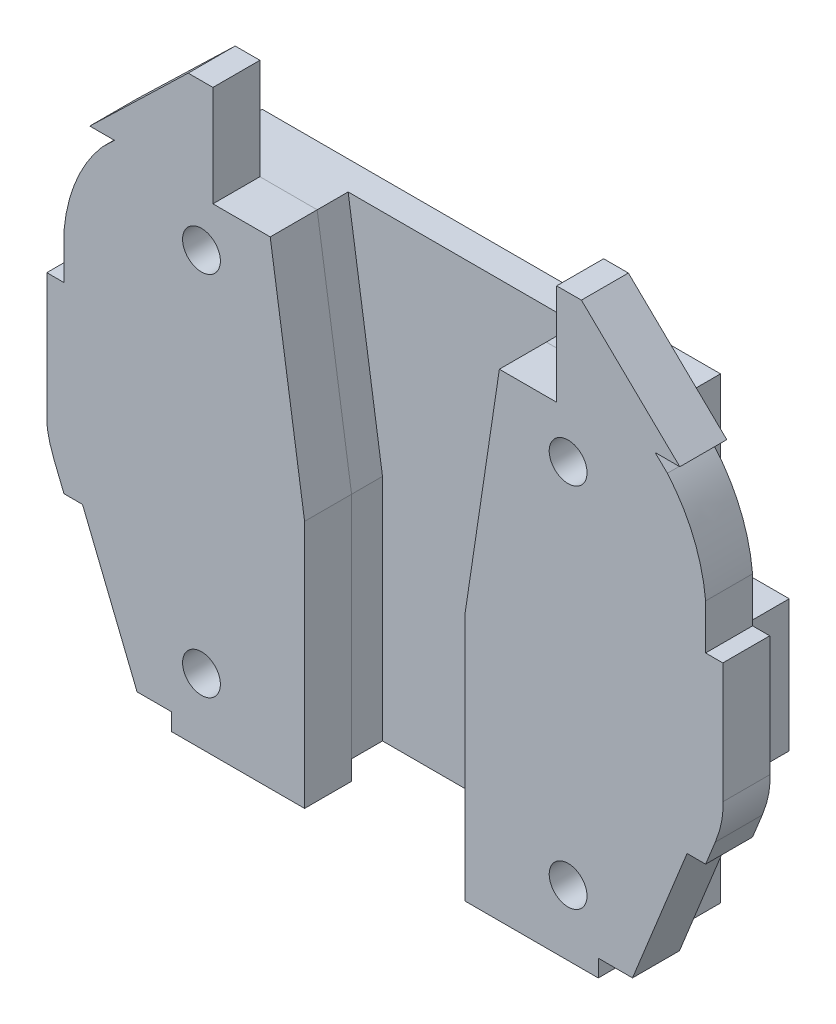
SolidWorks part; units mm, degrees
ref_plane "Front Plane" through (0, 0, 0) normal (0, 0, 1) x (1, 0, 0)
ref_plane "Top Plane" through (0, 0, 0) normal (0, 1, 0) x (1, 0, 0)
ref_plane "Right Plane" through (0, 0, 0) normal (1, 0, 0) x (0, 0, -1)
sketch "Sketch1" plane through (0, 0, 0) normal (0, 0, 1) x (1, 0, 0)
  line L0 (41, 42.4837) -> (1, 2.4837) construction
  line L1 (41, 2.4837) -> (1, 2.4837)
  line L2 (41, 2.4837) -> (41, 42.4837)
  line L3 (41, 42.4837) -> (1, 42.4837)
  line L4 (1, 2.4837) -> (1, 42.4837)
  line L5 (21, 42.4837) -> (21, 2.4837) construction
  line L6 (41, 22.4837) -> (1, 22.4837) construction
  line L7 (1, 42.4837) -> (41, 2.4837) construction
  line L9 (5, 38.4837) -> (37, 38.4837)
  line L10 (5, 38.4837) -> (5, 6.4837)
  line L11 (5, 6.4837) -> (37, 6.4837)
  line L12 (37, 38.4837) -> (37, 6.4837)
  line L13 (5, 38.4837) -> (37, 6.4837) construction
  line L14 (5, 6.4837) -> (37, 38.4837) construction
  line L40 (5, 3.0187) -> (5, 9.9487) construction
  line L41 (8, 9.4837) -> (2, 9.4837) construction
  line L42 (8, 9.4837) -> (8, 3.4837) construction
  line L43 (8, 3.4837) -> (2, 3.4837) construction
  line L44 (2, 9.4837) -> (2, 3.4837) construction
  line L45 (8, 9.4837) -> (2, 3.4837) construction
  line L46 (8, 3.4837) -> (2, 9.4837) construction
  line L47 (2, 4.7235) -> (5, 3.0187)
  line L48 (5, 3.0187) -> (8, 4.7499)
  line L49 (2, 8.2176) -> (5, 9.9487)
  line L50 (5, 9.9487) -> (8, 8.2176)
  line L51 (2, 4.7235) -> (2, 8.2176)
  line L52 (8, 4.7499) -> (8, 8.2176)
  circle A4 centre (5, 6.4837) radius 1.65
  circle A5 centre (5, 6.4837) radius 3.465 construction
  point P5 (21, 22.4837)
  point P41 (21, 22.4837)
  dimension "D2" = 40
  dimension "D3" = 40
  dimension "D1" = 32
extrude "Boss-Extrude1" add sketch "Sketch1" along normal blind 5.2 contours L4 L3 L2 L1
sketch "Sketch2" plane through (0, 0, -6) normal (0, 0, 1) x (1, 0, 0)
  line L0 (41, 2.4837) -> (41, 42.4837) construction
  line L1 (41, 10.9837) -> (1, 10.9837)
  line L2 (41, 10.9837) -> (41, 22.4837)
  line L3 (41, 22.4837) -> (1, 22.4837)
  line L4 (1, 10.9837) -> (1, 22.4837)
  line L5 (21, 22.4837) -> (21, 10.9837) construction
  line L6 (41, 16.7337) -> (1, 16.7337) construction
  line L7 (1, 2.4837) -> (1, 42.4837) construction
  line L8 (41, 42.4837) -> (1, 42.4837) construction
  line L9 (42, 22.7337) -> (0, 22.7337) construction
  point P72 (21, 16.7337)
  dimension "D1" = 11.5
  dimension "D2" = 0.25
  dimension "D3" = 20
extrude "Boss-Extrude2" add sketch "Sketch2" along normal up to surface (6 mm away) up to face at (21, 22.4837, 0)
sketch "Sketch3" plane through (0, 5.0004, 0) normal (0, -1, 0) x (1, 0, 0)
  circle A0 centre (11, -2.9068) radius 1.6
  circle A1 centre (31, -2.9068) radius 1.6
  dimension "D1" = 3.2
  dimension "D2" = 3.2
extrude "Cut-Extrude1" cut sketch "Sketch3" against normal up to surface (37.4833 mm away) up to face at (21, 42.4837, 2.6)
sketch "Sketch4" plane through (0, 0, 0) normal (0, 0, -1) x (-1, 0, 0)
  line L0 (-5, 6.4837) -> (1.6368, 6.4837) construction
  line L1 (-2.1, 9.3837) -> (-7.9, 9.3837)
  line L2 (-2.1, 9.3837) -> (-2.1, 3.5837)
  line L3 (-2.1, 3.5837) -> (-7.9, 3.5837)
  line L4 (-7.9, 9.3837) -> (-7.9, 3.5837)
  line L5 (-2.1, 9.3837) -> (-7.9, 3.5837) construction
  line L6 (-2.1, 3.5837) -> (-7.9, 9.3837) construction
  circle A0 centre (-5, 6.4837) radius 1.65
  dimension "D1" = 3.3
  dimension "D2" = 5.8
  dimension "D3" = 5.8
extrude "Cut-Extrude2" cut sketch "Sketch4" against normal up to surface (5.2 mm away) contours A0 up to face at (21, 22.4837, 5.2)
extrude "Cut-Extrude3" cut sketch "Sketch1<3>" along normal blind 3.3 contours L52 L50 L49 L51 L47 L48
sketch "Sketch1<3>" plane through (0, 0, 0) normal (0, 0, 1) x (1, 0, 0) same geometry as "Sketch1"
pattern_linear "LPattern1" count 2 spacing 32 along (1, 0, 0) of "Cut-Extrude3", "Cut-Extrude2"
pattern_linear "LPattern2" count 2 spacing 32 along (0, 1, 0) of "Cut-Extrude2", "Cut-Extrude3", "LPattern1"
sketch "Sketch6" plane through (0, 0, 5.2) normal (0, 0, 1) x (1, 0, 0)
  line L0 (21, 2.4837) -> (21, 42.4837) construction
  line L1 (41, 2.4837) -> (1, 2.4837) construction
  line L2 (41, 42.4837) -> (1, 42.4837) construction
  line L3 (14, 2.4837) -> (14, 22.4837)
  line L4 (14, 2.4837) -> (14, 22.4837) construction
  line L5 (14, 22.4837) -> (11, 42.4837)
  line L6 (14, 22.4837) -> (11, 42.4837) construction
  line L7 (28, 22.4837) -> (31, 42.4837)
  line L8 (28, 2.4837) -> (28, 22.4837)
  line L9 (28, 2.4837) -> (14, 2.4837)
  line L10 (31, 42.4837) -> (11, 42.4837)
  line L11 (14, 2.4837) -> (14, 0.7837)
  line L12 (-8.5, 34.0343) -> (-8.5, 19.5332)
  line L13 (-7.8447, 16.1617) -> (-1.6316, 0.7837)
  line L14 (3.8414, 51.2837) -> (6.0007, 51.2837)
  line L15 (38.1586, 51.2837) -> (35.9993, 51.2837)
  line L16 (1.8586, 47.2837) -> (-0.3007, 47.2837)
  line L17 (-7, 22.5332) -> (-8.5, 22.5332)
  line L18 (3.8414, 51.2837) -> (6.0007, 51.2837) construction
  line L19 (-7.8447, 37.4058) -> (-6.8435, 39.8838)
  line L20 (-4.7507, 42.9864) -> (3.8414, 51.2837)
  line L21 (-4.7507, 42.9864) -> (3.8414, 51.2837) construction
  line L22 (-1.6316, 0.7837) -> (14, 0.7837)
  line L23 (28, 2.4837) -> (28, 0.7837)
  line L24 (29.5, 2.4837) -> (29.5, 2.2837)
  line L25 (42.6198, 2.2837) -> (29.5, 2.2837)
  line L26 (46.7507, 42.9864) -> (38.1586, 51.2837)
  line L27 (50.5, 34.0343) -> (50.5, 19.5332)
  line L28 (49.8447, 16.1617) -> (43.6316, 0.7837)
  line L29 (43.6316, 0.7837) -> (28, 0.7837)
  line L30 (6.0007, 51.2837) -> (6.0007, 42.4837)
  line L31 (6.0007, 42.4837) -> (11, 42.4837)
  line L32 (35.9993, 42.4837) -> (31, 42.4837)
  line L33 (35.9993, 51.2837) -> (35.9993, 42.4837)
  line L34 (48.4539, 16.7236) -> (42.6198, 2.2837)
  line L35 (49, 33.9693) -> (49, 19.4865)
  line L36 (45.663, 41.9516) -> (37.5526, 49.7837)
  line L37 (37.5526, 49.7837) -> (37.4993, 49.7837)
  line L38 (37.4993, 49.7837) -> (37.4993, 40.9837)
  line L39 (37.4993, 40.9837) -> (31, 40.9837)
  line L40 (12.5, 2.4837) -> (12.5, 2.2837)
  line L41 (-0.6198, 2.2837) -> (12.5, 2.2837)
  line L42 (-6.4539, 16.7236) -> (-0.6198, 2.2837)
  line L43 (-7, 33.9693) -> (-7, 19.4865)
  line L44 (-3.663, 41.9516) -> (4.4474, 49.7837)
  line L45 (4.4474, 49.7837) -> (4.5007, 49.7837)
  line L46 (4.5007, 49.7837) -> (4.5007, 40.9837)
  line L47 (4.5007, 40.9837) -> (11, 40.9837)
  line L48 (-22.9464, 7.8027) -> (58.041, 7.8027) construction
  line L49 (-4.7507, 42.9864) -> (-2.5914, 42.9864)
  line L50 (58.041, 14.072) -> (-27.3823, 14.072) construction
  line L51 (-8.5, 30.0343) -> (-7, 30.0343)
  line L52 (-27.3823, 22.5332) -> (58.041, 22.5332) construction
  line L53 (-2.8496, 7.8027) -> (-4.4674, 7.8027)
  line L54 (58.041, 30.0343) -> (-27.3823, 30.0343) construction
  line L55 (-7.0003, 14.072) -> (-5.3825, 14.072)
  line L56 (-27.3823, 42.9864) -> (56.7736, 42.9864) construction
  line L57 (2.3684, 2.2837) -> (2.3684, 0.7837)
  line L58 (56.8152, 47.2837) -> (-27.3408, 47.2837) construction
  line L59 (2.3684, -8.0251) -> (2.3684, 59.5259) construction
  line L60 (9.3684, 2.2837) -> (9.3684, 0.7837)
  line L61 (9.3684, 59.5259) -> (9.3684, -6.8867) construction
  line L62 (32.6316, 2.2837) -> (32.6316, 0.7837)
  line L63 (32.6316, -6.8867) -> (32.6316, 60.9093) construction
  line L64 (39.6316, 2.2837) -> (39.6316, 0.7837)
  line L65 (39.6316, 60.9093) -> (39.6316, -6.8867) construction
  line L66 (44.8496, 7.8027) -> (46.4674, 7.8027)
  line L67 (49.0003, 14.072) -> (47.3825, 14.072)
  line L68 (49, 22.5332) -> (50.5, 22.5332)
  line L69 (50.5, 30.0343) -> (49, 30.0343)
  line L70 (46.7507, 42.9864) -> (44.5914, 42.9864)
  line L71 (40.1414, 47.2837) -> (42.3007, 47.2837)
  spline S0 degree 3 poles (-8.5, 34.0343) (-8.2221, 37.3131) (-6.9297, 40.5036) (-4.7507, 42.9864) knots 0 0 0 0 1 1 1 1
  spline S1 degree 2 poles (-7.8447, 16.1617) (-8.5, 17.7837) (-8.5, 19.5332) knots 0 0 0 1 1 1 weights 1 0.538462 1 construction
  spline S6 degree 3 poles (-7.8447, 16.1617) (-7.8555, 16.1886) (-8.2916, 17.2772) (-8.5722, 18.3733) (-8.5, 19.5332) knots 0 0 0 0 0.024714 1 1 1 1
  spline S8 degree 3 poles (50.5, 34.0343) (50.2221, 37.3131) (48.9297, 40.5036) (46.7507, 42.9864) knots 0 0 0 0 1 1 1 1
  spline S9 degree 3 poles (49.8447, 16.1617) (49.8555, 16.1886) (50.2916, 17.2772) (50.5722, 18.3733) (50.5, 19.5332) knots 0 0 0 0 0.024714 1 1 1 1
  spline S10 degree 1 poles (48.4539, 16.7236) (49, 19.4865) knots 0 0 1 1 construction
  spline S11 degree 1 poles (49, 33.9693) (45.663, 41.9516) knots 0 0 1 1 construction
  spline S12 degree 3 poles (48.4539, 16.7236) (48.55, 16.9616) (48.7326, 17.4571) (48.9152, 18.1409) (48.9972, 18.6946) (49.013, 19.0852) (49.0106, 19.3023) (49.0037, 19.4265) (49, 19.4865) knots 0 0 0 0 0.253262 0.506524 0.759786 0.886417 0.949733 1.013048 1.013048 1.013048 1.013048
  spline S13 degree 3 poles (49, 33.9693) (48.8701, 35.4274) (48.1614, 38.328) (46.6178, 40.8533) (45.663, 41.9516) knots 0.006919 0.006919 0.006919 0.006919 0.500067 0.993215 0.993215 0.993215 0.993215
  spline S14 degree 1 poles (-6.4539, 16.7236) (-7, 19.4865) knots 0 0 1 1 construction
  spline S15 degree 1 poles (-7, 33.9693) (-3.663, 41.9516) knots 0 0 1 1 construction
  spline S16 degree 3 poles (-6.4539, 16.7236) (-6.55, 16.9616) (-6.7326, 17.4571) (-6.9152, 18.1409) (-6.9972, 18.6946) (-7.013, 19.0852) (-7.0106, 19.3023) (-7.0037, 19.4265) (-7, 19.4865) knots 0 0 0 0 0.253262 0.506524 0.759786 0.886417 0.949733 1.013048 1.013048 1.013048 1.013048
  spline S17 degree 3 poles (-7, 33.9693) (-6.8701, 35.4274) (-6.1614, 38.328) (-4.6178, 40.8533) (-3.663, 41.9516) knots 0.006919 0.006919 0.006919 0.006919 0.500067 0.993215 0.993215 0.993215 0.993215
  circle M4 centre (37, 38.4837) radius 1.65
  circle M5 centre (5, 38.4837) radius 1.65
  circle M6 centre (37, 6.4837) radius 1.65
  circle M7 centre (5, 6.4837) radius 1.65
  line M8 (1, 2.4837) -> (41, 2.4837)
  line M9 (41, 2.4837) -> (41, 42.4837)
  line M10 (41, 42.4837) -> (1, 42.4837)
  line M11 (1, 42.4837) -> (1, 2.4837)
  dimension "D1" = 1.5
  dimension "D3" = 3
  dimension "D4" = 4
  dimension "D5" = 4
  dimension "D6" = 4
  dimension "D7" = 7
  dimension "D8" = 4
  dimension "D9" = 7
  dimension "D10" = 8.4612
  dimension "D11" = 6.2692
  dimension "D2" = 1.5
extrude "Cut-Extrude4" cut sketch "Sketch6" against normal blind 2.7 contours L0 L10 L5 L3 M8 region at (21, 23.7741, 5.2)
extrude "Boss-Extrude3" add sketch "Sketch6<3>" along normal blind 4.1 separate body contours L28 S9 L27 S8 L26 L23 L29 M10 M9 M8 | L8 L7 M8 M9 M10 M6 M4 | L3 L5 M10 M11 M8 M7 M5 | L36 L71 L26 L15 L33 L38 L37 M10 | S17 L43 S16 L42 L41 L40 L46 L45 L44 M8 M11 M10 | L27 L69 L35 L68 | S12 L34 L67 L28 S9 L27 L68 L35 | L64 L25 L62 L29 | L62 L25 L24 L23 L29 M8 | L45 L46 L30 L14 L20 L16 L44 M10 | L51 L12 L17 L43 | L42 S16 L43 L17 L12 S6 L13 L55 | L60 L41 L57 L22 | L41 L60 L22 L11 L40 M8 | L20 L49 L44 L16 | L71 L36 L70 L26 region at (7.2415, 21.6379, 5.2) region at (11.749, 1.5689, 5.2) region at (30.251, 1.5689, 5.2) region at (34.7585, 21.6379, 5.2) region at (-2.0056, 26.2829, 5.2) region at (44.0056, 26.2829, 5.2) region at (5.8684, 1.5337, 5.2) region at (5.2507, 42.592, 5.2) region at (36.1316, 1.5337, 5.2) region at (36.1075, 46.8837, 5.2) region at (-1.4461, 45.1351, 5.2) region at (-7.3673, 18.2268, 5.2) region at (43.4461, 45.1351, 5.2) region at (49.3673, 18.2268, 5.2) region at (-7.75, 26.2837, 5.2) region at (49.75, 26.2837, 5.2)
sketch "Sketch6<3>" plane through (0, 0, 5.2) normal (0, 0, 1) x (1, 0, 0) same geometry as "Sketch6"
